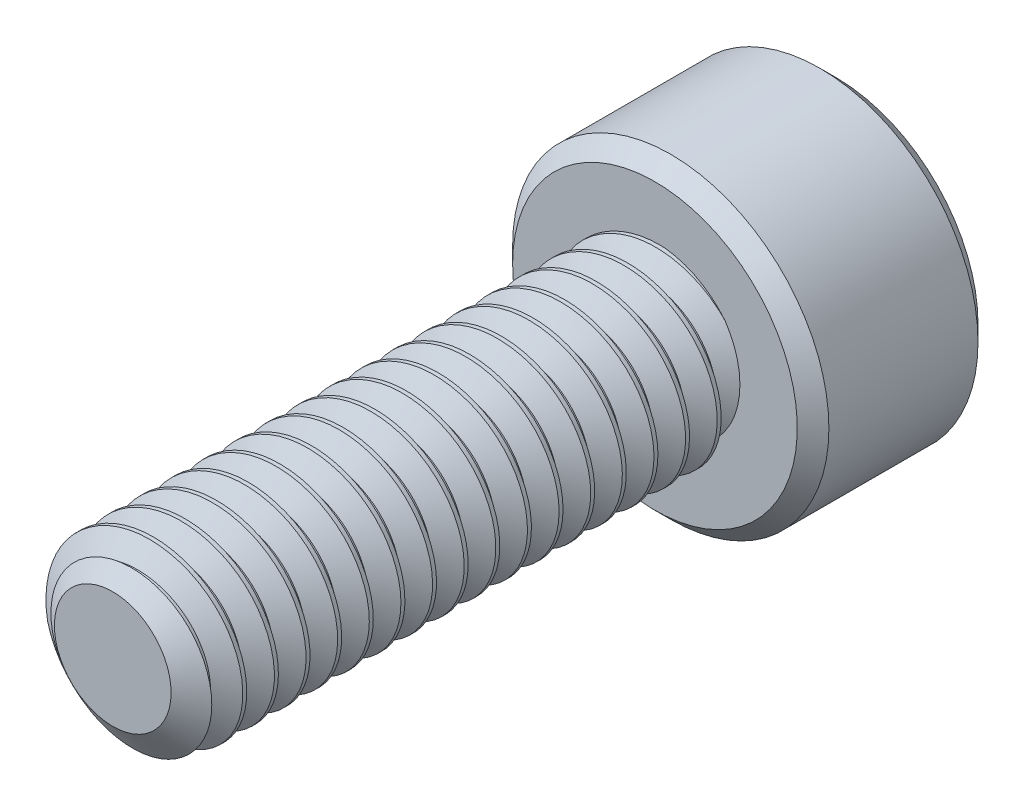
SolidWorks part; units mm, degrees
ref_plane "Front Plane" through (0, 0, 0) normal (0, 0, 1) x (1, 0, 0)
ref_plane "Top Plane" through (0, 0, 0) normal (0, 1, 0) x (1, 0, 0)
ref_plane "Right Plane" through (0, 0, 0) normal (1, 0, 0) x (0, 0, -1)
sketch "Sketch1" plane through (0, 0, 0) normal (0, 0, 1) x (1, 0, 0)
  circle A0 centre (0, 0) radius 2
  dimension "OD" = 4
extrude "Extrude1" add sketch "Sketch1" against normal blind 12
sketch "Sketch2" plane through (0, 0, 0) normal (0, 0, 1) x (1, 0, 0)
  circle A0 centre (0, 0) radius 2 construction
  circle A1 centre (0, 0) radius 2
curve "Helix/Spiral1" pitch 0.7 height 12.7 radius 2 centre (0, 0, 0) axis (0, 0, -1) start towards (0, 1, 0) parameters "pitch"=0.7
sketch "Sketch3" plane through (0, 0, 0) normal (1, 0, 0) x (0, 0, -1)
  line L0 (-0.6125, 2) -> (-0.35, 1.5453)
  line L1 (-0.35, 1.5453) -> (-0.2625, 1.5453)
  line L2 (-0.2625, 1.5453) -> (0, 2)
  line L3 (-0.6125, 2) -> (0, 2)
  line L4 (-0.3062, 2) -> (-0.3062, 1.5453) construction
  line L5 (-0.4812, 1.7727) -> (-0.1312, 1.7727) construction
  line L6 (0, 2) -> (0, -2) construction
  dimension "D1" = 0.0875
  dimension "D2" = 0.35
  dimension "D3" = 60
sweep "Cut-Sweep1" cut profiles "Sketch3" path "Helix/Spiral1" align with end faces yes
sketch "Sketch4" plane through (0, 0, 0) normal (1, 0, 0) x (0, 0, -1)
  line L0 (0.4962, 2) -> (0, 1.2913)
  line L1 (0, 1.2913) -> (0, 2)
  line L2 (0.4962, 2) -> (0, 2)
  line L3 (-0.6125, 2) -> (0, 2) construction
  line L4 (0, 0) -> (7.0209, 0) construction
  dimension "D1" = 55
  dimension "D2" = 0.254
revolve "Cut-Revolve1" cut sketch "Sketch4" angle 360 about L4
sketch "Sketch5" plane through (0, 0, 0) normal (1, 0, 0) x (0, 0, -1)
  line L0 (12, -0.9741) -> (12, 1.9864) construction
  line L1 (12, 2.127) -> (1.2679, 2.127)
  line L2 (12, 2.127) -> (12, 0)
  line L3 (12, 0) -> (1, 0)
  line L4 (1, 1.127) -> (1, 0)
  line L5 (1.2679, 2.127) -> (1, 1.127)
  line L6 (0, 0) -> (1, 0) construction
  point P3 (1, 2.127)
  point P10 (1, 2.127)
  dimension "D1" = 1
  dimension "D2" = 0.127
  dimension "D3" = 15
  dimension "Thread Min" = 1
revolve "partially thread" [suppressed] add sketch "Sketch5" angle 360 about L6
sketch "Sketch6" plane through (0, 0, -12) normal (0, 0, -1) x (-1, 0, 0)
  circle A0 centre (0, 0) radius 3.5
  dimension "head dia" = 7
extrude "Extrude2" add sketch "Sketch6" along normal blind 4
sketch "Sketch7" plane through (0, 0, -16) normal (0, 0, -1) x (-1, 0, 0)
  line L1 (0, 1.7321) -> (-1.5, 0.866)
  line L2 (-1.5, 0.866) -> (-1.5, -0.866)
  line L3 (-1.5, -0.866) -> (0, -1.7321)
  line L4 (0, -1.7321) -> (1.5, -0.866)
  line L5 (1.5, -0.866) -> (1.5, 0.866)
  line L6 (1.5, 0.866) -> (0, 1.7321)
  circle A0 centre (0, 0) radius 1.5 construction
  dimension "hex dia" = 3
extrude "Cut-Extrude1" cut sketch "Sketch7" against normal blind 2.25
sketch "Sketch8" plane through (0, 0, -16) normal (0, 0, -1) x (-1, 0, 0)
  circle A0 centre (0, 0) radius 1.7321
extrude "Cut-Extrude2" cut sketch "Sketch8" against normal through all draft 45
chamfer "Chamfer1" distance 0.35 angle 45 2 edges at (-3.5, 0, -16) (-3.5, 0, -12)
sketch "Sketch9" plane through (0, 0, 0) normal (1, 0, 0) x (0, 0, -1)
  line L0 (0, 2) -> (0, -2) construction
  line L1 (3.85, 2) -> (3.85, -2) construction
  dimension "D1" = 3.85
equation "\"D3@Helix/Spiral1\" = \"screw length@Extrude1\"+\"pitch@Helix/Spiral1\""
equation "\"D1@Sketch3\" = \"pitch@Helix/Spiral1\"*.125"
equation "\"D2@Sketch3\" = \"pitch@Helix/Spiral1\"*.5"
equation "\"D1@Cut-Extrude1\" = \"hex dia@Sketch7\"*.75"
equation "\"D1@Chamfer1\" = \"head dia@Sketch6\"*.05"
equation "\"D1@Sketch9\" = \"pitch@Helix/Spiral1\"*5.5"
